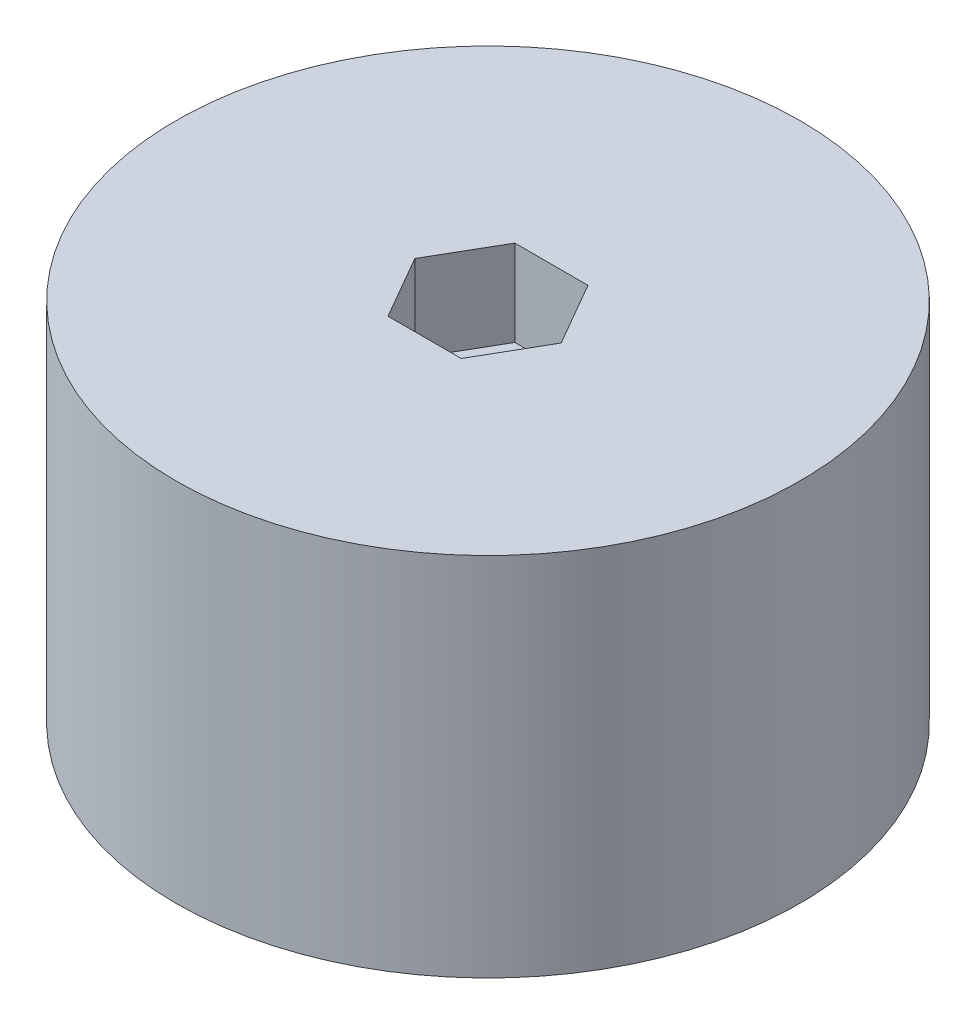
SolidWorks part; units mm, degrees
ref_plane "Front Plane" through (0, 0, 0) normal (0, 0, 1) x (1, 0, 0)
ref_plane "Top Plane" through (0, 0, 0) normal (0, 1, 0) x (1, 0, 0)
ref_plane "Right Plane" through (0, 0, 0) normal (1, 0, 0) x (0, 0, -1)
sketch "Sketch1" plane through (0, 0, 0) normal (0, 1, 0) x (1, 0, 0)
  circle A0 centre (0, 0) radius 21.75
  circle A1 centre (0, 0) radius 3
  dimension "D1" = 43.5
  dimension "D2" = 6
extrude "Boss-Extrude1" add sketch "Sketch1" along normal blind 25.5
sketch "Sketch2" plane through (0, 25.5, 0) normal (0, 1, 0) x (1, 0, 0)
  line L1 (5.1, 0) -> (2.55, 4.4167)
  line L2 (2.55, 4.4167) -> (-2.55, 4.4167)
  line L3 (-2.55, 4.4167) -> (-5.1, 0)
  line L4 (-5.1, 0) -> (-2.55, -4.4167)
  line L5 (-2.55, -4.4167) -> (2.55, -4.4167)
  line L6 (2.55, -4.4167) -> (5.1, 0)
  circle A0 centre (0, 0) radius 4.4167 construction
  dimension "D1" = 5.1
extrude "Cut-Extrude1" cut sketch "Sketch2" against normal blind 6
